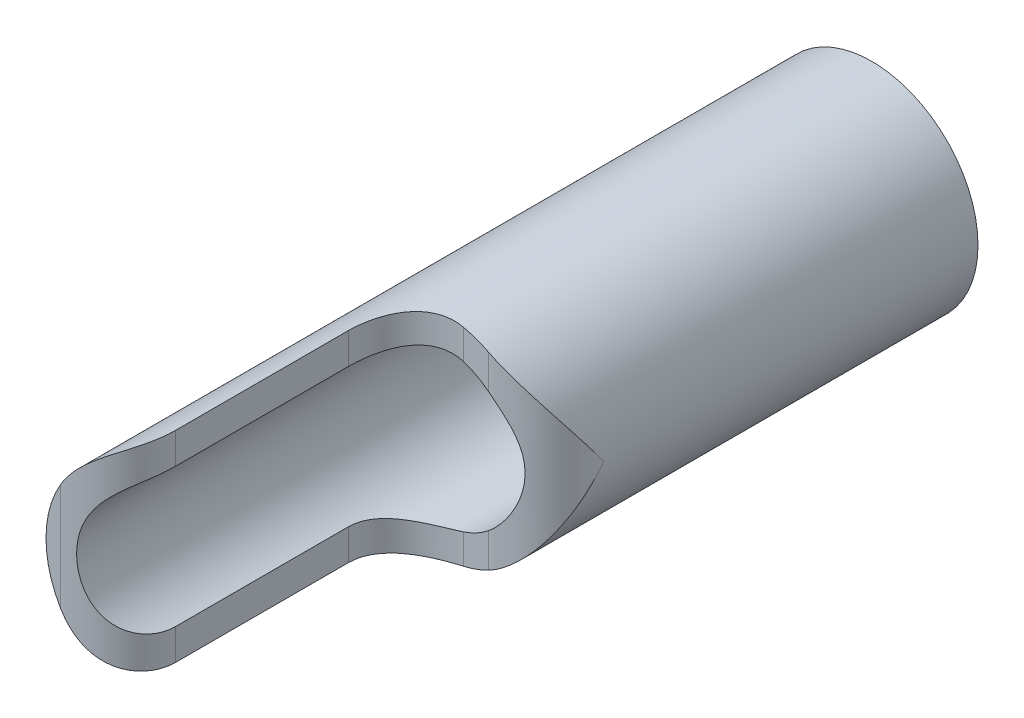
SolidWorks part; units mm, degrees
ref_plane "Front Plane" through (0, 0, 0) normal (0, 0, 1) x (1, 0, 0)
ref_plane "Top Plane" through (0, 0, 0) normal (0, 1, 0) x (1, 0, 0)
ref_plane "Right Plane" through (0, 0, 0) normal (1, 0, 0) x (0, 0, -1)
sketch "Sketch1" plane through (0, 0, 0) normal (0, 0, 1) x (1, 0, 0)
  circle A0 centre (0, 0) radius 0.7375
  circle A1 centre (0, 0) radius 0.5375
  dimension "D1" = 1.475
  dimension "D2" = 0.2
extrude "Boss-Extrude1" add sketch "Sketch1" along normal blind 5
sketch "Sketch3" plane through (0, 0, 0) normal (0, 1, 0) x (1, 0, 0)
  line L0 (-0.7375, -5) -> (-0.6375, -5)
  line L1 (-0.7375, -5) -> (0.7375, -5) construction
  line L2 (-0.2375, -4.6) -> (-0.2375, -3.4)
  line L3 (0.1625, -3) -> (0.3375, -3)
  line L4 (0.7375, -5) -> (0.7375, 0) construction
  line L5 (0.7375, -2.6) -> (0.7375, -2.2904)
  line L6 (0.7375, -2.2904) -> (1.0406, -2.2904)
  line L7 (1.0406, -2.2904) -> (1.0406, -5.2893)
  line L8 (1.0406, -5.2893) -> (-0.7375, -5.2893)
  line L9 (-0.7375, -5.2893) -> (-0.7375, -5)
  arc A0 (0.3375, -3) -> (0.7375, -2.6) centre (0.3375, -2.6) ccw
  arc A1 (-0.6375, -5) -> (-0.2375, -4.6) centre (-0.6375, -4.6) ccw
  arc A2 (-0.2375, -3.4) -> (0.1625, -3) centre (0.1625, -3.4) cw
  point P15 (0.7375, -3)
  point P18 (-0.2375, -5)
  dimension "D1" = 0.4
  dimension "D2" = 0.4
  dimension "D3" = 0.4
extrude "Cut-Extrude1" cut sketch "Sketch3" against normal blind 2 and the other way blind 2
